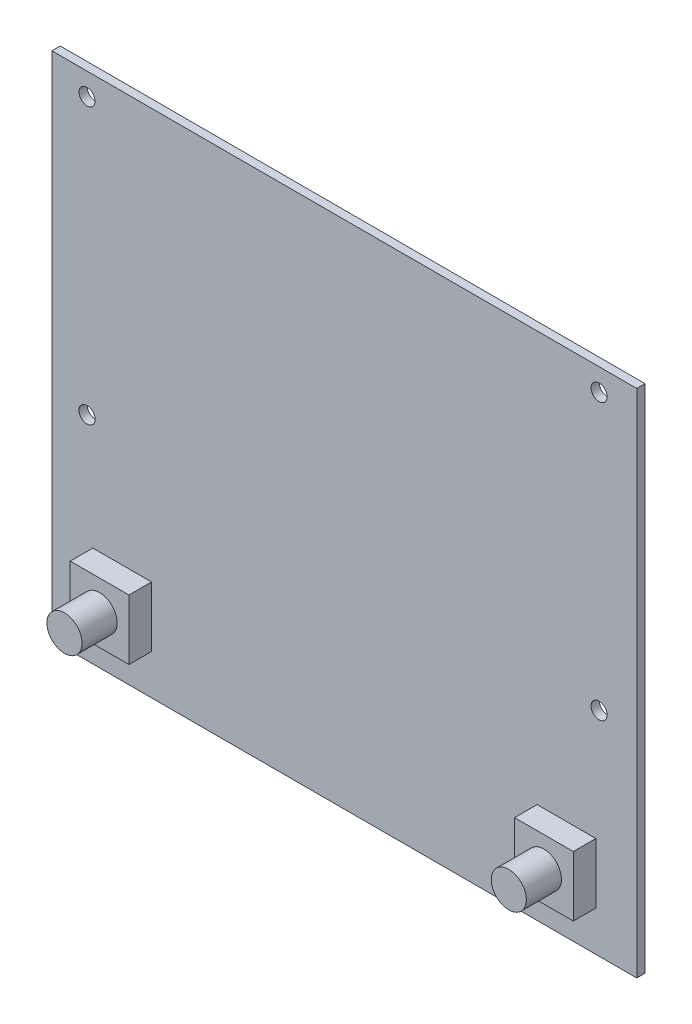
SolidWorks part; units mm, degrees
ref_plane "Front Plane" through (0, 0, 0) normal (0, 0, 1) x (1, 0, 0)
ref_plane "Top Plane" through (0, 0, 0) normal (0, 1, 0) x (1, 0, 0)
ref_plane "Right Plane" through (0, 0, 0) normal (1, 0, 0) x (0, 0, -1)
sketch "Sketch1" plane through (0, 0, 0) normal (0, 0, 1) x (1, 0, 0)
  line L1 (-58.2701, 50.8698) -> (58.2701, 50.8698)
  line L2 (-58.2701, 50.8698) -> (-58.2701, -50.8698)
  line L3 (-58.2701, -50.8698) -> (58.2701, -50.8698)
  line L4 (58.2701, 50.8698) -> (58.2701, -50.8698)
  line L5 (-58.2701, 50.8698) -> (58.2701, -50.8698) construction
  line L6 (-58.2701, -50.8698) -> (58.2701, 50.8698) construction
  circle A0 centre (-51.2699, 46.4502) radius 1.6002
  circle A1 centre (50.7695, 46.4502) radius 1.6002
  circle A2 centre (50.7695, -8.4493) radius 1.6002
  circle A3 centre (-51.2699, -8.4493) radius 1.6002
  point P0 (0, 0)
  dimension "D3" = 3.2004
  dimension "D6" = 3.2004
  dimension "D7" = 3.2004
  dimension "D8" = 3.2004
  dimension "D1" = 101.7397
  dimension "D2" = 116.5403
  dimension "D4" = 7.0002
  dimension "D5" = 4.4196
  dimension "D9" = 7.5006
  dimension "D10" = 54.8996
extrude "Boss-Extrude1" add sketch "Sketch1" along normal blind 1.6561
sketch "Sketch2" plane through (0, 0, 1.6561) normal (0, 0, 1) x (1, 0, 0)
  line L0 (0, 50.8698) -> (0, -50.8698) construction
  line L1 (-50.1193, -42.8688) -> (-38.42, -42.8688)
  line L2 (-50.1193, -42.8688) -> (-50.1193, -30.8699)
  line L3 (-50.1193, -30.8699) -> (-38.42, -30.8699)
  line L4 (-38.42, -42.8688) -> (-38.42, -30.8699)
  line L5 (58.2701, 50.8698) -> (-58.2701, 50.8698) construction
  line L36 (-58.2701, -50.8698) -> (58.2701, -50.8698) construction
  line L37 (50.1193, -30.8699) -> (38.42, -30.8699)
  line L38 (38.42, -42.8688) -> (38.42, -30.8699)
  line L39 (50.1193, -42.8688) -> (38.42, -42.8688)
  line L40 (50.1193, -42.8688) -> (50.1193, -30.8699)
  dimension "D1" = 8.1509
  dimension "D2" = 8.001
  dimension "D3" = 11.6992
  dimension "D4" = 11.999
  dimension "D5" = 8.1509
  dimension "D6" = 8.001
  dimension "D7" = 11.6992
  dimension "D8" = 11.999
extrude "Boss-Extrude2" add sketch "Sketch2" along normal blind 4.5
sketch "Sketch3" plane through (0, 0, 6.1561) normal (0, 0, 1) x (1, 0, 0)
  line L0 (-44.2697, -42.8688) -> (-44.2697, -30.8699) construction
  line L1 (-50.1193, -42.8688) -> (-38.42, -42.8688) construction
  line L2 (-38.42, -30.8699) -> (-50.1193, -30.8699) construction
  line L3 (-50.1193, -36.8694) -> (-38.42, -36.8694) construction
  line L4 (-50.1193, -30.8699) -> (-50.1193, -42.8688) construction
  line L5 (-38.42, -42.8688) -> (-38.42, -30.8699) construction
  line L6 (38.42, -42.8688) -> (50.1193, -30.8699) construction
  line L7 (50.1193, -42.8688) -> (38.42, -30.8699) construction
  circle A0 centre (-44.2697, -36.8694) radius 3.5
  circle A1 centre (44.2697, -36.8694) radius 3.5
  point P16 (-44.2697, -36.8694)
  point P25 (0, 0)
  point P26 (44.2697, -36.8694)
  dimension "D1" = 7
  dimension "D2" = 7
extrude "Boss-Extrude3" add sketch "Sketch3" along normal blind 7
